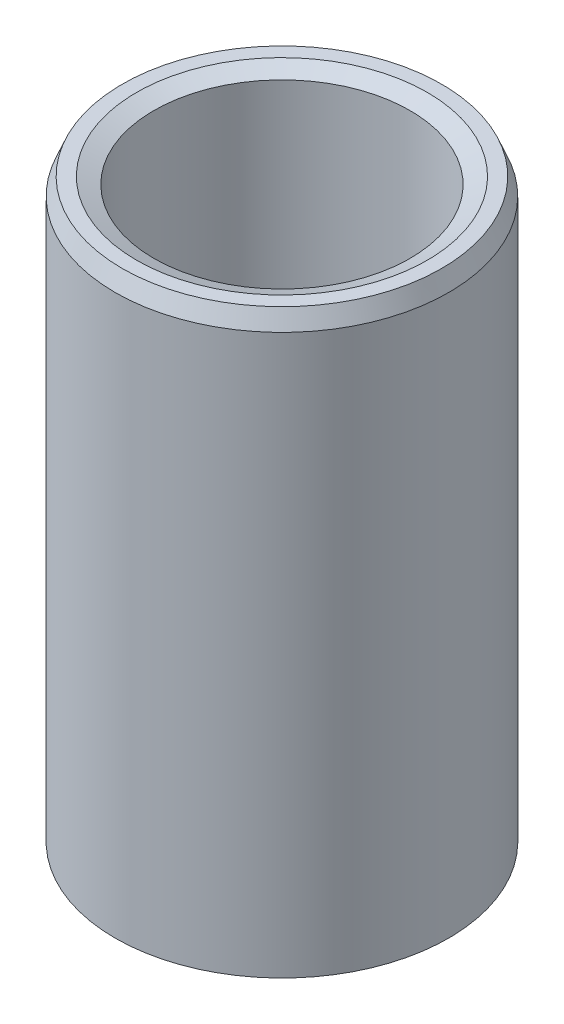
SolidWorks part; units mm, degrees
ref_plane "Front Plane" through (0, 0, 0) normal (0, 0, 1) x (1, 0, 0)
ref_plane "Top Plane" through (0, 0, 0) normal (0, 1, 0) x (1, 0, 0)
ref_plane "Right Plane" through (0, 0, 0) normal (1, 0, 0) x (0, 0, -1)
sketch "Sketch1" plane through (0, 0, 0) normal (0, 1, 0) x (1, 0, 0)
  circle A0 centre (0, 0) radius 25
  dimension "SLEEVE_OD" = 50
extrude "Boss-Extrude1" add sketch "Sketch1" along normal blind 87.4803
sketch "Sketch2" plane through (0, 0, 0) normal (0, 1, 0) x (1, 0, 0)
  circle A0 centre (0, 0) radius 19.2074
  dimension "BORE_D" = 38.4148
extrude "Cut-Extrude1" cut sketch "Sketch2" along normal through all
chamfer "Chamfer1" distance 2.5906 angle 22.209 4 edges at (0, 87.4803, 19.2074) (0, 0, 19.2074) (0, 0, 25) (0, 87.4803, 25) first distance on face at (0, 87.4803, 19.2074) first distance on face at (0, 0, 19.2074) first distance on face at (0, 87.4803, 25)
